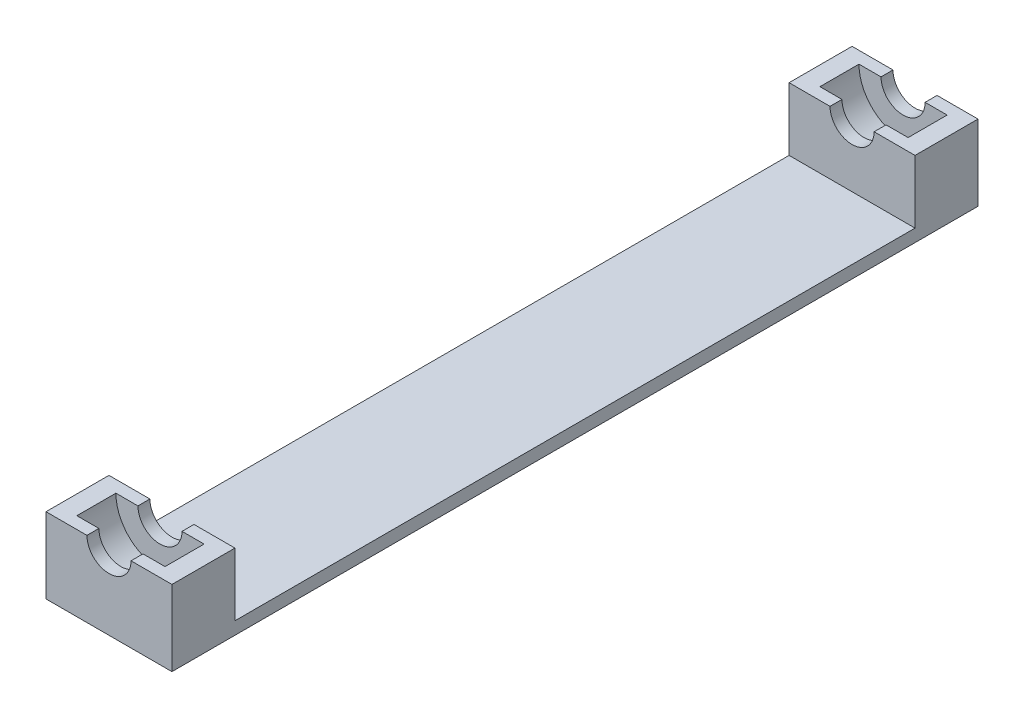
SolidWorks part; units mm, degrees
ref_plane "Front Plane" through (0, 0, 0) normal (0, 0, 1) x (1, 0, 0)
ref_plane "Top Plane" through (0, 0, 0) normal (0, 1, 0) x (1, 0, 0)
ref_plane "Right Plane" through (0, 0, 0) normal (1, 0, 0) x (0, 0, -1)
sketch "Sketch1" plane through (0, 0, 0) normal (1, 0, 0) x (0, 0, -1)
  line L0 (0, 21.9578) -> (0, -21.9578) construction
  line L1 (-32, 0.5) -> (32, 0.5)
  line L2 (-32, 0.5) -> (-32, -0.5)
  line L3 (-32, -0.5) -> (32, -0.5)
  line L4 (32, 0.5) -> (32, -0.5)
  line L5 (0, -0.5) -> (0, 0.5) construction
  line L6 (-32, 0) -> (32, 0) construction
  line L7 (27, 5.5) -> (32, 5.5)
  line L8 (27, 5.5) -> (27, 0.5)
  line L9 (27, 0.5) -> (32, 0.5)
  line L10 (32, 5.5) -> (32, 0.5)
  line L11 (29.5, 0.5) -> (29.5, 5.5) construction
  line L12 (27, 3) -> (32, 3) construction
  line L13 (-32, 5.5) -> (-32, 0.5)
  line L14 (-27, 5.5) -> (-32, 5.5)
  line L15 (-27, 5.5) -> (-27, 0.5)
  point P0 (0, 0)
  point P4 (0, 0)
  point P5 (29.5, 3)
  point P9 (0, 0)
  point P12 (0, 0)
  dimension "D1" = 64
  dimension "D2" = 1
  dimension "D3" = 5
  dimension "D4" = 5
extrude "Boss-Extrude1" add sketch "Sketch1" along normal blind 10 contours L15 L14 L13 L1 | L10 L7 L8 L1 | L1 L4 L3 L2 region at (0, 3, 29.5) region at (0, 3, -29.5)
ref_plane "Plane1" through (0, 0, 29.5) normal (0, 0, 1) x (1, 0, 0)
sketch "Sketch2" plane through (0, 0, 29.5) normal (0, 0, 1) x (1, 0, 0)
  line L1 (0, 5.5) -> (10, 5.5) construction
  line L2 (0, 5.5) -> (0, -0.5) construction
  line L3 (0, -0.5) -> (10, -0.5) construction
  line L4 (10, 5.5) -> (10, -0.5) construction
  line L5 (5, -0.5) -> (5, 5.5) construction
  line L6 (0, 2.5) -> (10, 2.5) construction
  circle A1 centre (5, 5.5) radius 3.5
  circle A2 centre (5, 5.5) radius 1.75
  point P0 (5, 2.5)
  point P6 (0, 0)
  dimension "D1" = 7
  dimension "D2" = 3.5
extrude "Cut-Extrude1" cut sketch "Sketch2" against normal mid plane 3.1
ref_plane "Plane3" through (0, 0, -29.5) normal (0, 0, 1) x (1, 0, 0)
ref_plane "Plane4" through (0, 0, 0) normal (0, 0, 1) x (1, 0, 0)
extrude "Cut-Extrude2" cut sketch "Sketch2<2>" against normal mid plane 13.2 contours A2 region at (5, 5.5, 29.5)
sketch "Sketch2<2>" plane through (0, 0, 29.5) normal (0, 0, 1) x (1, 0, 0) same geometry as "Sketch2"
mirror "Mirror1" about plane through (0, 0, 0) normal (0, 0, 1) of "Cut-Extrude1"
mirror "Mirror2" about plane through (0, 0, 0) normal (0, 0, 1) of "Cut-Extrude2"
